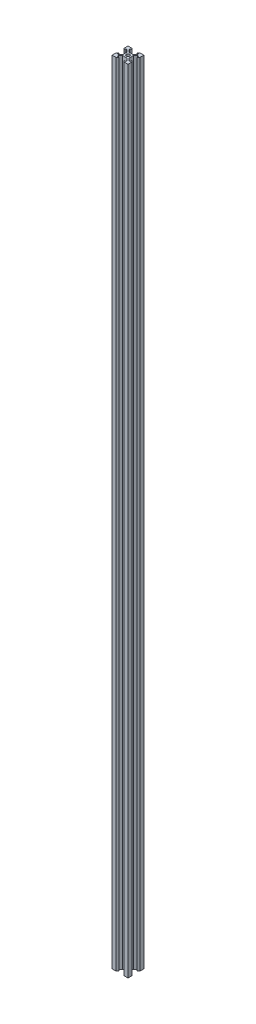
SolidWorks part; units mm, degrees
ref_plane "Piano frontale" through (0, 0, 0) normal (0, 0, 1) x (1, 0, 0)
ref_plane "Piano superiore" through (0, 0, 0) normal (0, 1, 0) x (1, 0, 0)
ref_plane "Piano destro" through (0, 0, 0) normal (1, 0, 0) x (0, 0, -1)
sketch "Schizzo1" plane through (0, 0, 0) normal (0, 1, 0) x (1, 0, 0)
  line L0 (-10, 10) -> (-4.9, 10)
  line L1 (-10, 10) -> (10, 10) construction
  line L2 (-10, 10) -> (-10, -10) construction
  line L3 (-10, -10) -> (10, -10) construction
  line L4 (10, 10) -> (10, -10) construction
  line L5 (-10, 10) -> (10, -10) construction
  line L6 (-10, -10) -> (10, 10) construction
  line L7 (-4.9, 10) -> (-3.1, 8.2)
  line L8 (-3.1, 8.2) -> (-5.4993, 8.2)
  line L9 (-5.4993, 8.2) -> (-5.4993, 6.56)
  line L10 (-5.4993, 6.56) -> (-2.84, 3.9007)
  line L11 (-2.84, 3.9007) -> (0, 3.9007)
  line L12 (-3.9007, 2.84) -> (-3.9007, 0)
  line L13 (-6.56, 5.4993) -> (-3.9007, 2.84)
  line L14 (-8.2, 5.4993) -> (-6.56, 5.4993)
  line L15 (-8.2, 3.1) -> (-8.2, 5.4993)
  line L16 (-10, 4.9) -> (-8.2, 3.1)
  line L17 (-10, 10) -> (-10, 4.9)
  line L18 (10, 10) -> (10, 4.9)
  line L19 (10, 4.9) -> (8.2, 3.1)
  line L20 (8.2, 3.1) -> (8.2, 5.4993)
  line L21 (8.2, 5.4993) -> (6.56, 5.4993)
  line L22 (6.56, 5.4993) -> (3.9007, 2.84)
  line L23 (2.84, 3.9007) -> (0, 3.9007)
  line L24 (5.4993, 6.56) -> (2.84, 3.9007)
  line L25 (5.4993, 8.2) -> (5.4993, 6.56)
  line L26 (3.1, 8.2) -> (5.4993, 8.2)
  line L27 (4.9, 10) -> (3.1, 8.2)
  line L28 (10, 10) -> (4.9, 10)
  line L29 (3.9007, 2.84) -> (3.9007, 0)
  line L30 (10, -10) -> (4.9, -10)
  line L31 (4.9, -10) -> (3.1, -8.2)
  line L32 (3.1, -8.2) -> (5.4993, -8.2)
  line L33 (5.4993, -8.2) -> (5.4993, -6.56)
  line L34 (5.4993, -6.56) -> (2.84, -3.9007)
  line L35 (3.9007, -2.84) -> (3.9007, 0)
  line L36 (6.56, -5.4993) -> (3.9007, -2.84)
  line L37 (8.2, -5.4993) -> (6.56, -5.4993)
  line L38 (8.2, -3.1) -> (8.2, -5.4993)
  line L39 (10, -4.9) -> (8.2, -3.1)
  line L40 (10, -10) -> (10, -4.9)
  line L41 (2.84, -3.9007) -> (0, -3.9007)
  line L42 (-10, -10) -> (-10, -4.9)
  line L43 (-10, -4.9) -> (-8.2, -3.1)
  line L44 (-8.2, -3.1) -> (-8.2, -5.4993)
  line L45 (-8.2, -5.4993) -> (-6.56, -5.4993)
  line L46 (-6.56, -5.4993) -> (-3.9007, -2.84)
  line L47 (-2.84, -3.9007) -> (0, -3.9007)
  line L48 (-5.4993, -6.56) -> (-2.84, -3.9007)
  line L49 (-5.4993, -8.2) -> (-5.4993, -6.56)
  line L50 (-3.1, -8.2) -> (-5.4993, -8.2)
  line L51 (-4.9, -10) -> (-3.1, -8.2)
  line L52 (-10, -10) -> (-4.9, -10)
  line L53 (-3.9007, -2.84) -> (-3.9007, 0)
  circle A0 centre (0, 0) radius 2.1
  point P0 (0, 0)
  point P61 (0, 0)
  dimension "D9" = 4.2
  dimension "D1" = 20
  dimension "D2" = 1.8
  dimension "D3" = 1.64
  dimension "D4" = 45
  dimension "D5" = 6.2
  dimension "D6" = 0.75
  dimension "D7" = 2.84
  dimension "D8" = 4
extrude "Estrusione-Estrusione1" [suppressed] add sketch "Schizzo1" along normal blind 500
extrude "Estrusione-Estrusione2" add sketch "Schizzo1<2>" along normal blind 1000
sketch "Schizzo1<2>" plane through (0, 0, 0) normal (0, 1, 0) x (1, 0, 0) same geometry as "Schizzo1"
